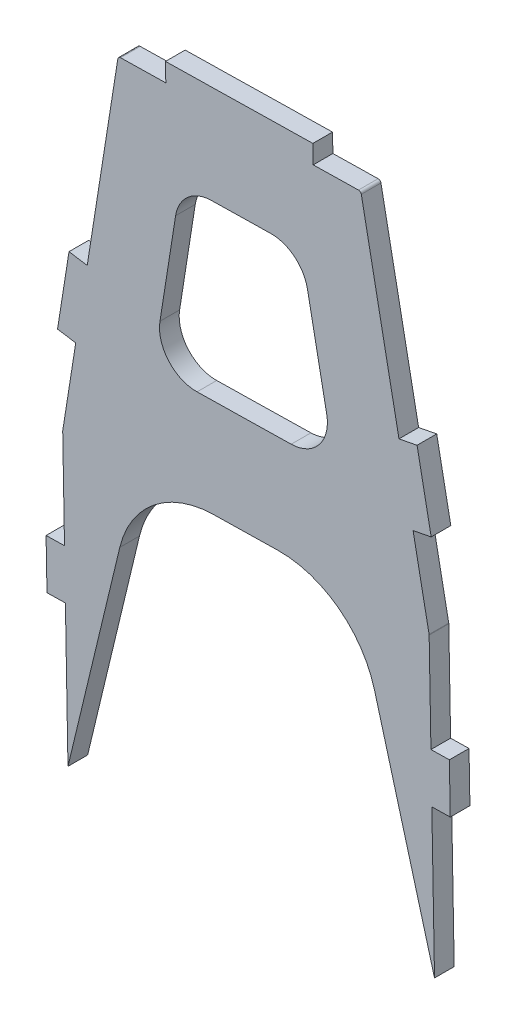
SolidWorks part; units mm, degrees
ref_plane "Front Plane" through (0, 0, 0) normal (0, 0, 1) x (1, 0, 0)
ref_plane "Top Plane" through (0, 0, 0) normal (0, 1, 0) x (1, 0, 0)
ref_plane "Right Plane" through (0, 0, 0) normal (1, 0, 0) x (0, 0, -1)
sketch "Sketch5" plane through (0, 0, -50.8) normal (0, 0, -1) x (-1, 0, 0)
  line L0 (-56.2179, -96.0796) -> (-52.0841, -74.9047) construction
  line L1 (38.4505, -97.8087) -> (35.0927, -76.4969) construction
  line L2 (39.7972, -75.7557) -> (35.0927, -76.4969) construction
  line L3 (39.7972, -75.7557) -> (36.8323, -56.9379) construction
  line L4 (36.8323, -56.9379) -> (32.1279, -57.6791) construction
  line L5 (-56.7584, -73.9922) -> (-52.0841, -74.9047) construction
  line L6 (-56.7584, -73.9922) -> (-53.1084, -55.2951) construction
  line L7 (-53.1084, -55.2951) -> (-48.4341, -56.2076) construction
  line L8 (-48.4341, -56.2076) -> (-38.7006, -6.3488) construction
  line L9 (-26.1883, -1.2053) -> (-26.2752, -5.967) construction
  line L10 (-37.9642, -5.7535) -> (-26.2752, -5.967) construction
  line L11 (32.1279, -57.6791) -> (24.2216, -7.4981) construction
  line L12 (23.5074, -6.8763) -> (11.8184, -6.6628) construction
  line L13 (11.9054, -1.9011) -> (11.8184, -6.6628) construction
  line L14 (-7.1414, -1.5532) -> (-26.1883, -1.2053) construction
  line L15 (-7.1414, -1.5532) -> (11.9054, -1.9011) construction
  line L16 (-56.2179, -96.0796) -> (-52.0841, -74.9047)
  line L17 (38.4505, -97.8087) -> (35.0927, -76.4969)
  line L18 (39.7972, -75.7557) -> (35.0927, -76.4969)
  line L19 (39.7972, -75.7557) -> (36.8323, -56.9379)
  line L20 (36.8323, -56.9379) -> (32.1279, -57.6791)
  line L21 (-56.7584, -73.9922) -> (-52.0841, -74.9047)
  line L22 (-56.7584, -73.9922) -> (-53.1084, -55.2951)
  line L23 (-53.1084, -55.2951) -> (-48.4341, -56.2076)
  line L24 (-48.4341, -56.2076) -> (-38.7006, -6.3488)
  line L25 (-26.1883, -1.2053) -> (-26.2752, -5.967)
  line L26 (-37.9642, -5.7535) -> (-26.2752, -5.967)
  line L27 (32.1279, -57.6791) -> (24.2216, -7.4981)
  line L28 (23.5074, -6.8763) -> (11.8184, -6.6628)
  line L29 (11.9054, -1.9011) -> (11.8184, -6.6628)
  line L30 (-7.1414, -1.5532) -> (-26.1883, -1.2053)
  line L31 (-7.1414, -1.5532) -> (11.9054, -1.9011)
  line L32 (-56.2179, -96.0796) -> (38.4505, -97.8087)
  line L33 (19.1098, -97.4554) -> (8.0462, -27.2348)
  line L34 (-23.2568, -26.6631) -> (8.0462, -27.2348)
  line L35 (-23.2568, -26.6631) -> (-36.8772, -96.4328)
  line L36 (-31.9354, -71.1188) -> (15.0957, -71.9778)
  line L37 (19.1098, -97.4554) -> (37.1017, -172.2667)
  line L38 (-36.8772, -96.4328) -> (-57.6206, -172.2667)
  line L39 (-56.6953, -121.603) -> (-56.2314, -96.2072) construction
  line L40 (37.9955, -123.3325) -> (38.4593, -97.9367) construction
  line L41 (-57.623, -172.3945) -> (-56.9272, -134.3009) construction
  line L42 (-56.9272, -134.3009) -> (-61.6889, -134.2139) construction
  line L55 (-61.457, -121.516) -> (-61.6889, -134.2139) construction
  line L56 (-56.6953, -121.603) -> (-61.457, -121.516) construction
  line L57 (-56.6953, -121.603) -> (-56.2314, -96.2072) construction
  line L58 (-57.623, -172.3945) -> (-56.9272, -134.3009)
  line L59 (-56.9272, -134.3009) -> (-61.6889, -134.2139)
  line L60 (-61.457, -121.516) -> (-61.6889, -134.2139)
  line L61 (-56.6953, -121.603) -> (-61.457, -121.516)
  line L62 (-56.6953, -121.603) -> (-56.2314, -96.2072)
  line L63 (37.0678, -174.124) -> (37.7635, -136.0304) construction
  line L64 (43.221, -98.0237) -> (42.7572, -123.4195) construction
  line L65 (37.7635, -136.0304) -> (42.5253, -136.1174) construction
  line L66 (42.7572, -123.4195) -> (42.5253, -136.1174) construction
  line L67 (37.9955, -123.3325) -> (42.7572, -123.4195) construction
  line L68 (37.9955, -123.3325) -> (38.4593, -97.9367) construction
  line L69 (37.0678, -174.124) -> (37.7635, -136.0304)
  line L70 (43.221, -98.0237) -> (42.7572, -123.4195)
  line L71 (37.7635, -136.0304) -> (42.5253, -136.1174)
  line L72 (42.7572, -123.4195) -> (42.5253, -136.1174)
  line L73 (37.9955, -123.3325) -> (42.7572, -123.4195)
  line L74 (37.9955, -123.3325) -> (38.4593, -97.9367)
  arc A0 (-37.9642, -5.7535) -> (-38.7006, -6.3488) centre (-37.9777, -6.49) ccw construction
  arc A1 (24.2216, -7.4981) -> (23.5074, -6.8763) centre (23.494, -7.6127) ccw construction
  arc A2 (-37.9642, -5.7535) -> (-38.7006, -6.3488) centre (-37.9777, -6.49) ccw
  arc A3 (24.2216, -7.4981) -> (23.5074, -6.8763) centre (23.494, -7.6127) ccw
  arc A8 (-56.2179, -96.0796) -> (-56.2314, -96.2072) centre (-55.4949, -96.2207) ccw construction
  arc A9 (-56.2179, -96.0796) -> (-56.2314, -96.2072) centre (-55.4949, -96.2207) ccw
  arc A10 (38.4593, -97.9367) -> (38.4505, -97.8087) centre (37.7228, -97.9233) ccw construction
  arc A11 (38.4593, -97.9367) -> (38.4505, -97.8087) centre (37.7228, -97.9233) ccw
  dimension "D1" = 19.05
  dimension "D2" = 19.05
  dimension "D3" = 25.4
  dimension "D4" = 25.4
  dimension "D5" = 76.2
extrude "Boss-Extrude2" add sketch "Sketch5" along normal blind 5.08 contours L35 L36 L33 L34 | L32 L37 | L32 L38 | L30 L25 L26 A2 L24 L23 L22 L21 L16 L32 L17 L18 L19 L20 L27 A3 L28 L29 L31 region at (50.9207, -122.0717, -50.8) region at (-32.2315, -123.0689, -50.8) region at (8.0398, -50.7411, -50.8)
fillet "Fillet2" radius 9.525 4 edges at (23.2568, -26.6631, -53.34) (-8.0462, -27.2348, -53.34) (31.9354, -71.1188, -53.34) (-15.0957, -71.9778, -53.34)
fillet "Fillet3" radius 25.4 2 edges at (-19.1098, -97.4554, -53.34) (36.8772, -96.4328, -53.34)
